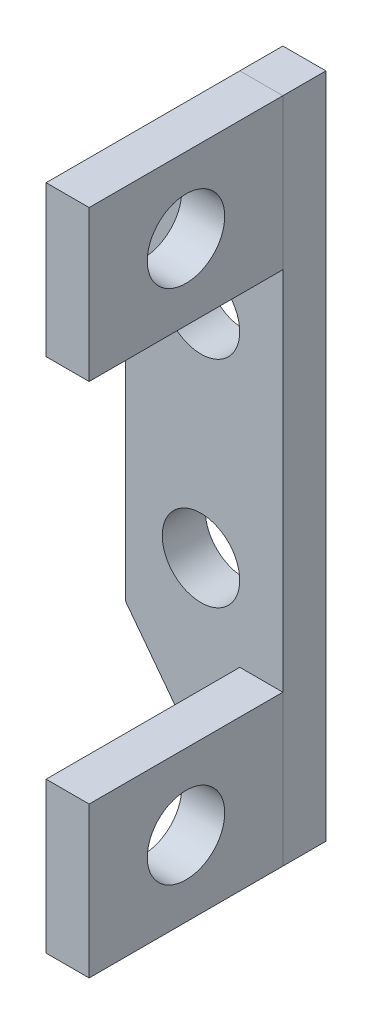
SolidWorks part; units mm, degrees
ref_plane "Front Plane" through (0, 0, 0) normal (0, 0, 1) x (1, 0, 0)
ref_plane "Top Plane" through (0, 0, 0) normal (0, 1, 0) x (1, 0, 0)
ref_plane "Right Plane" through (0, 0, 0) normal (1, 0, 0) x (0, 0, -1)
sketch "Sketch2" plane through (0, 0, 0) normal (0, 0, 1) x (1, 0, 0)
  line L0 (-10, 226.4206) -> (-10, 176.4206) construction
  line L1 (-10, 196.9206) -> (-2.6956, 196.9206)
  line L2 (-10, 196.9206) -> (-10, 213.9206)
  line L3 (-10, 213.9206) -> (-2.6956, 213.9206)
  line L4 (-2.6956, 196.9206) -> (-2.6956, 213.9206)
  line L5 (-2.4956, 220.74) -> (-2.4956, 195.8582) construction
  line L6 (-6.5, 200.4206) -> (-10, 200.4206) construction
  line L7 (-6.5, 200.4206) -> (-6.5, 196.9206) construction
  line L8 (-10, 205.4206) -> (-2.6956, 205.4206) construction
  line L9 (-6.5, 200.4206) -> (-6.5, 210.4206) construction
  line L10 (-2.6956, 196.9206) -> (-2.6956, 189.9206)
  line L11 (-2.6956, 189.9206) -> (-4.6956, 189.9206)
  line L12 (-4.6956, 189.9206) -> (-10, 196.9206)
  line L13 (-2.6956, 213.9206) -> (-2.6956, 220.9206)
  line L14 (-2.6956, 220.9206) -> (-4.6956, 220.9206)
  line L15 (-4.6956, 220.9206) -> (-10, 213.9206)
  circle A0 centre (-6.5, 200.4206) radius 1.75 construction
  circle A1 centre (-6.5, 200.4206) radius 1.75 construction
  point P15 (-6.5, 205.4206)
  dimension "D1" = 0.2
  dimension "D2" = 7
  dimension "D3" = 2
extrude "Boss-Extrude1" add sketch "Sketch2" along normal blind 2 contours L12 L11 L10 L1 | L14 L15 L3 L13 | L1 L4 L3 L2 region at (-6.3478, 205.4206, 0) region at (-5.2737, 194.0857, 0) region at (-5.2737, 216.7555, 0)
sketch "Sketch3" plane through (0, 0, 2) normal (0, 0, 1) x (1, 0, 0)
sketch "Sketch5" plane through (0, 0, 2) normal (0, 0, 1) x (1, 0, 0)
  point P0 (-6.5, 200.4206)
  point P3 (-6.5, 210.4206)
hole_wizard "M3 Clearance Hole1" positions "Sketch5" profile "Sketch4" hole size "M3" standard "ANSI Metric" end condition through all
sketch "Sketch4" plane through (-6.5, 200.4206, 2) normal (1, 0, 0) x (0, -1, 0)
  line L0 (0, 0) -> (0, 2)
  line L1 (0, 2) -> (1.8, 2)
  line L2 (1.8, 2) -> (1.8, 0)
  line L5 (1.8, 0) -> (0, 0)
  line L11 (0, -6.35) -> (0, 107.95) construction
  dimension "Thru Hole Dia." = 3.6
  dimension "Thru Hole Depth" = 2
sketch "Sketch6" plane through (0, 0, 2) normal (0, 0, 1) x (1, 0, 0)
  line L0 (-10, 205.4206) -> (-2.6956, 205.4206) construction
  line L1 (-2.6956, 213.9206) -> (-4.6956, 213.9206)
  line L2 (-2.6956, 213.9206) -> (-2.6956, 220.9206)
  line L3 (-2.6956, 220.9206) -> (-4.6956, 220.9206)
  line L4 (-4.6956, 213.9206) -> (-4.6956, 220.9206)
  line L7 (-2.6956, 189.9206) -> (-4.6956, 189.9206)
  line L8 (-4.6956, 196.9206) -> (-4.6956, 189.9206)
  line L9 (-2.6956, 196.9206) -> (-4.6956, 196.9206)
  line L10 (-2.6956, 196.9206) -> (-2.6956, 189.9206)
  line L12 (-2.6956, 220.9206) -> (-2.6956, 189.9206) construction
  line L13 (-10, 196.9206) -> (-10, 213.9206) construction
  line L14 (-2.6956, 220.9206) -> (-4.6956, 220.9206) construction
  point P7 (-10, 205.4206)
  point P9 (-2.6956, 205.4206)
  point P15 (0, 0)
  point P17 (0, 0)
  point P19 (0, 0)
  point P20 (-2.6956, 213.7798)
  point P21 (-4.6956, 220.9206)
  dimension "D1" = 7
  dimension "D2" = 2
extrude "Boss-Extrude2" add sketch "Sketch6" along normal blind 9 separate body
sketch "Sketch7" plane through (-4.6956, 0, 0) normal (-1, 0, 0) x (0, 0, 1)
  point P0 (6.5, 193.4206)
  point P2 (6.5, 217.4206)
hole_wizard "M3 Clearance Hole2" positions "Sketch7" profile "Sketch8" hole size "M3" standard "ANSI Metric" end condition through all
sketch "Sketch8" plane through (-4.6956, 193.4206, 6.5) normal (0, 1, 0) x (0, 0, 1)
  line L0 (0, 0) -> (0, 2)
  line L1 (0, 2) -> (1.8, 2)
  line L2 (1.8, 2) -> (1.8, 0)
  line L5 (1.8, 0) -> (0, 0)
  line L11 (0, -6.35) -> (0, 107.95) construction
  dimension "Thru Hole Dia." = 3.6
  dimension "Thru Hole Depth" = 2
